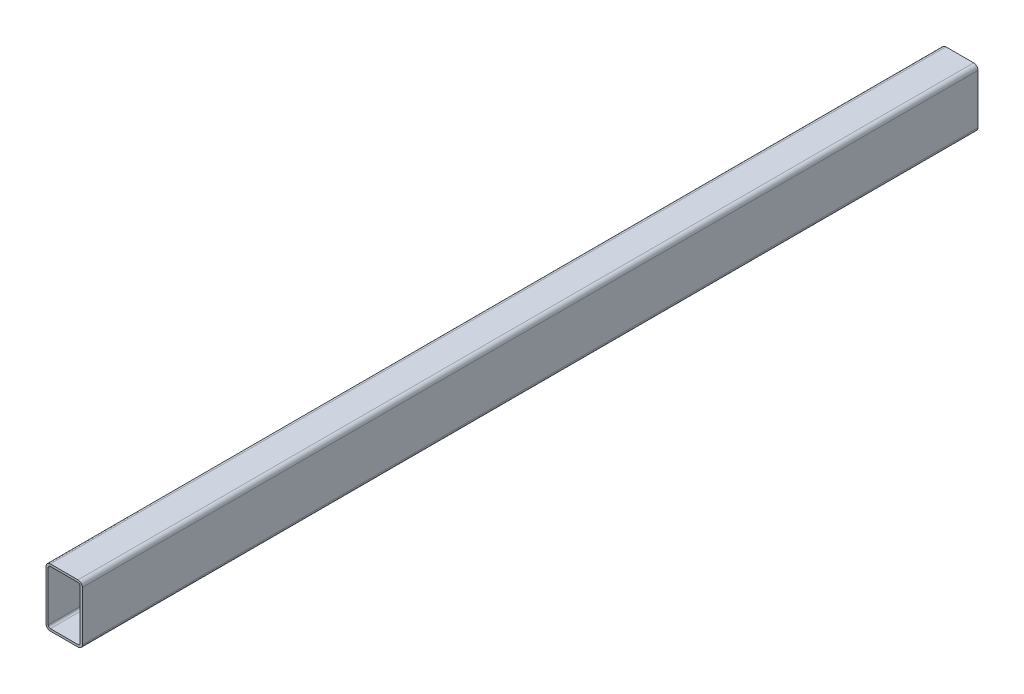
SolidWorks part; units mm, degrees
ref_plane "Front Plane" through (0, 0, 0) normal (0, 0, 1) x (1, 0, 0)
ref_plane "Top Plane" through (0, 0, 0) normal (0, 1, 0) x (1, 0, 0)
ref_plane "Right Plane" through (0, 0, 0) normal (1, 0, 0) x (0, 0, -1)
sketch "Sketch1" plane through (0, 0, 0) normal (0, 0, 1) x (1, 0, 0)
  line L0 (19, 37) -> (-19, 37)
  line L1 (19, -40) -> (-19, -40)
  line L2 (25, -34) -> (25, 34)
  line L3 (19, 40) -> (-19, 40)
  line L4 (-25, -34) -> (-25, 34)
  line L5 (25, -40) -> (-25, 40) construction
  line L6 (25, 40) -> (-25, -40) construction
  line L7 (-22, -34) -> (-22, 34)
  line L8 (19, -37) -> (-19, -37)
  line L9 (22, -34) -> (22, 34)
  arc A0 (-19, -40) -> (-25, -34) centre (-19, -34) cw
  arc A1 (19, -40) -> (25, -34) centre (19, -34) ccw
  arc A2 (25, 34) -> (19, 40) centre (19, 34) ccw
  arc A3 (-19, 40) -> (-25, 34) centre (-19, 34) ccw
  arc A4 (-19, 37) -> (-22, 34) centre (-19, 34) ccw
  arc A5 (-19, -37) -> (-22, -34) centre (-19, -34) cw
  arc A6 (19, -37) -> (22, -34) centre (19, -34) ccw
  arc A7 (22, 34) -> (19, 37) centre (19, 34) ccw
  point P0 (0, 0)
  dimension "D1" = 6
  dimension "D3" = 80
  dimension "D4" = 50
  dimension "D2" = 3
extrude "Boss-Extrude1" add sketch "Sketch1" along normal mid plane 1230
equation "\"M5_tap\"=4.2mm       ' Below you can do mesurements as follows: cm, mm, ft, in, m, "
equation "\"M5_clearence\"=5.5mm"
equation "\"M6_tap\"=5mm"
equation "\"M6_clearence\"=6.6mm"
equation "\"work_area_width\"=1100mm"
equation "\"work_area_depth\"=900mm"
equation "\"D3@Sketch1\"=\"steel_gantry_width\""
equation "\"D4@Sketch1\"=\"steel_gantry_height\""
equation "\"D1@Sketch1\"=\"steel_gantry_radius\""
equation "\"D2@Sketch1\"=\"steel_gantry_wall_thickness\""
equation "\"D1@Boss-Extrude1\"=\"work_area_width\" + \"steel_sides_height\" + \"steel_rollers_width\""
equation "\"steel_base_width\"=80mm"
equation "\"steel_base_height\"=50mm"
equation "\"steel_base_wall_thickness\"=3mm"
equation "\"steel_base_radius\"=6mm"
equation "\"steel_sides_width\"=80mm    'this tube is rotated so flip width/height"
equation "\"steel_sides_height\"=50mm    'this tube is rotated so flip width/height"
equation "\"steel_sides_wall_thickness\"=3mm"
equation "\"steel_sides_radius\"=6mm"
equation "\"steel_gantry_width\"=80mm    'this tube is rotated so flip width/height"
equation "\"steel_gantry_height\"=50mm    'this tube is rotated so flip width/height"
equation "\"steel_gantry_wall_thickness\"=3mm"
equation "\"steel_gantry_radius\"=6mm"
equation "\"steel_rollers_width\"=80mm"
equation "\"steel_rollers_height\"=50mm    'keep as low as possible as this increases how big plastic parts are"
equation "\"steel_rollers_wall_thickness\"=3mm"
equation "\"steel_rollers_radius\"=6mm"
equation "\"steel_zbox_width\"=80mm     'if the gantry height (rotated) is too thick, a wider zbox is necessary"
equation "\"steel_zbox_height\"=50mm    'hole patteren changes as the zbox and gantry height (rotated) changes."
equation "\"steel_zbox_wall_thickness\"=3mm"
equation "\"steel_zbox_radius\"=6mm"
